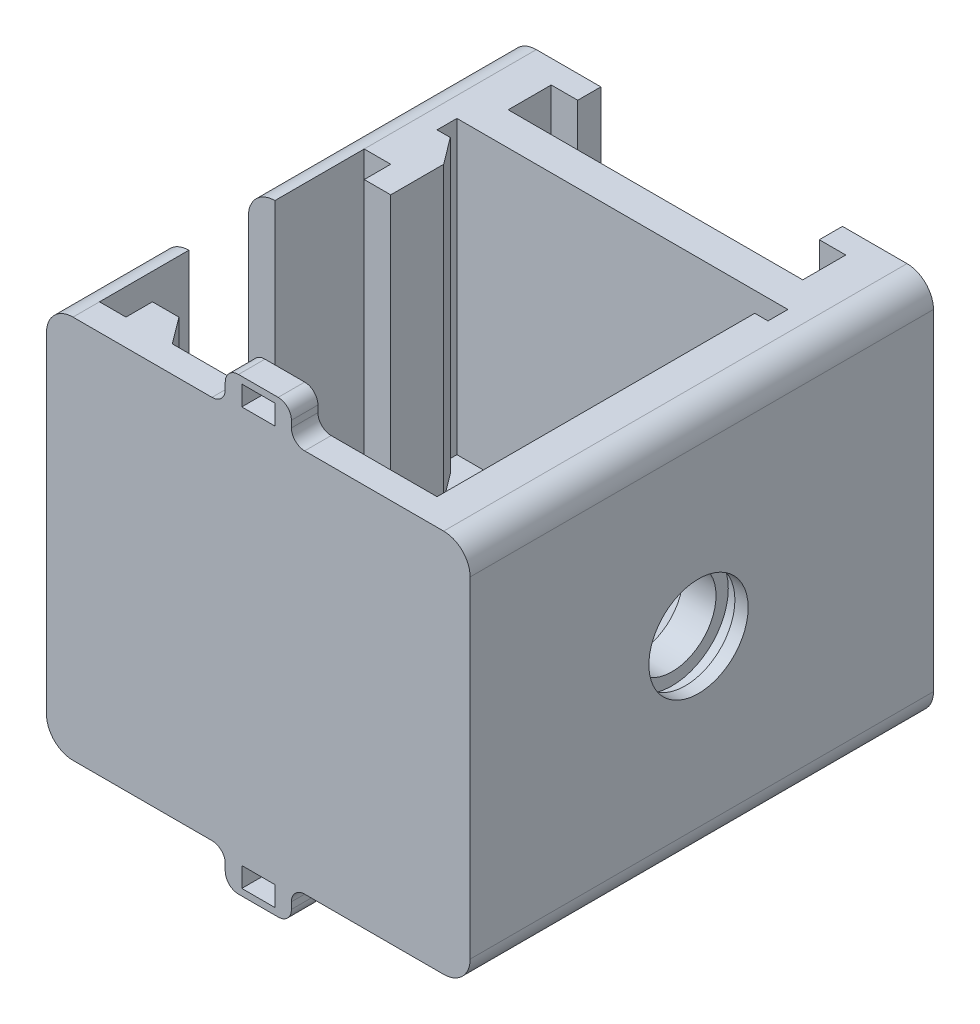
SolidWorks part; units mm, degrees
material "UNOBTANIUM"
ref_plane "Top Plane" through (0, 0, 0) normal (0, 0, 1) x (1, 0, 0)
ref_plane "Right Plane" through (0, 0, 0) normal (0, 1, 0) x (1, 0, 0)
ref_plane "Front Plane" through (0, 0, 0) normal (1, 0, 0) x (0, 0, -1)
ref_axis "x-axis" through (-17.6, 0, 0) along (1, 0, 0)
ref_axis "y-axis" through (0, -14.85, 0) along (0, 1, 0)
ref_axis "z-axis" through (0, 0, 36.75) along (0, 0, -1)
sketch "Sketch1" plane through (0, 0, 0) normal (0, 0, 1) x (1, 0, 0)
  line L1 (-16, 14.5) -> (16, 14.5)
  line L2 (-16, 14.5) -> (-16, -14.5)
  line L3 (-16, -14.5) -> (16, -14.5)
  line L4 (16, 14.5) -> (16, -14.5)
  line L5 (-16, 14.5) -> (16, -14.5) construction
  line L6 (-16, -14.5) -> (16, 14.5) construction
  point P0 (0, 0)
  dimension "D1" = 32
  dimension "D2" = 29
extrude "Boss-Extrude1" add sketch "Sketch1" along normal blind 35
fillet "Fillet1" radius 2 4 edges at (16, -14.5, 17.5) (16, 14.5, 17.5) (-16, -14.5, 17.5) (-16, 14.5, 17.5)
sketch "Sketch2" plane through (0, -14.5, 0) normal (0, -1, 0) x (1, 0, 0)
  line L0 (-9.125, 0) -> (-9.125, 1.75)
  line L1 (-14, 0) -> (14, 0) construction
  line L2 (-9.125, 1.75) -> (-11.125, 1.75)
  line L3 (-11.125, 1.75) -> (-11.125, 5)
  line L4 (-11.125, 5) -> (11.125, 5)
  line L5 (11.125, 5) -> (11.125, 1.75)
  line L6 (11.125, 1.75) -> (9.125, 1.75)
  line L7 (9.125, 1.75) -> (9.125, 0)
  line L9 (-9.125, 0) -> (9.125, 0)
  point P4 (0, 0)
  dimension "D1" = 18.25
  dimension "D2" = 1.75
  dimension "D3" = 3.25
  dimension "D4" = 22.25
extrude "Slot for Coil" cut sketch "Sketch2" against normal through all both and the other way through all
sketch "Sketch3" plane through (0, -14.5, 0) normal (0, -1, 0) x (1, 0, 0)
  line L0 (-9.125, 0) -> (-9.125, 1.75)
  line L1 (-9.125, 1.75) -> (-11.125, 1.75)
  line L2 (-11.125, 1.75) -> (-11.125, 5)
  line L3 (-11.125, 5) -> (11.125, 5)
  line L4 (11.125, 5) -> (11.125, 1.75)
  line L5 (11.125, 1.75) -> (9.125, 1.75)
  line L6 (9.125, 1.75) -> (9.125, 0)
  line L7 (9.125, 0) -> (-9.125, 0)
extrude "Boss-Extrude2" add sketch "Sketch3" against normal blind 7
sketch "Sketch4" plane through (0, 0, 1.75) normal (0, 0, -1) x (-1, 0, 0)
  line L1 (-9.125, 7.5) -> (-9.125, 6.5)
  line L2 (-9.125, 14.5) -> (-9.125, -7.5) construction
  arc A0 (-9.125, 7.5) -> (-9.125, 6.5) centre (-9.5, 7) cw
  dimension "D1" = 0.625
  dimension "D2" = 0.25
  dimension "D3" = 7
extrude "Boss-Extrude3" add sketch "Sketch4" along normal up to surface (1.75 mm away) up to face at (0, 1.1667, 0)
mirror "Mirror1" about plane through (0, 0, 0) normal (1, 0, 0) of "Boss-Extrude3"
sketch "Sketch5" plane through (0, 0, 0) normal (0, 0, -1) x (-1, 0, 0)
  line L0 (9.125, -7.5) -> (-9.125, -7.5) construction
  line L1 (-1, -7.5) -> (1, -7.5)
  line L2 (-1, -7.5) -> (-1, -14.5)
  line L3 (-1, -14.5) -> (1, -14.5)
  line L4 (1, -7.5) -> (1, -14.5)
  line L5 (14, -14.5) -> (-14, -14.5) construction
  point P8 (0, -7.5)
  dimension "D1" = 2
extrude "Cut-Extrude2" cut sketch "Sketch5" against normal offset from surface (33 mm away) 2 up to face at (0, 0, 35)
sketch "Sketch6" plane through (0, 14.5, 0) normal (0, 1, 0) x (1, 0, 0)
  line L0 (-12.5, -7.5) -> (-12.5, -9)
  line L1 (-12.5, -9) -> (-11.5, -9)
  line L2 (-11.5, -9) -> (-11.5, -33)
  line L3 (-11.5, -33) -> (11.5, -33)
  line L4 (11.5, -33) -> (11.5, -9)
  line L5 (11.5, -9) -> (12.5, -9)
  line L6 (12.5, -9) -> (12.5, -7.5)
  line L7 (12.5, -7.5) -> (-12.5, -7.5)
  line L8 (11.125, -5) -> (-11.125, -5) construction
  line L9 (0, -7.5) -> (0, -5) construction
  line L10 (14, -35) -> (-14, -35) construction
  dimension "D1" = 2.5
  dimension "D2" = 1.5
  dimension "D3" = 1
  dimension "D4" = 25
  dimension "D5" = 2
extrude "Cut-Extrude3" cut sketch "Sketch6" against normal up to surface (22 mm away) up to face at (7.0833, -7.5, 2.25)
sketch "Sketch7" plane through (0, -14.5, 0) normal (0, -1, 0) x (1, 0, 0)
  line L0 (1, 0) -> (14, 0) construction
  line L1 (1, 0) -> (-1, 0)
  line L2 (1, 0) -> (1, 33)
  line L3 (1, 33) -> (-1, 33)
  line L4 (-1, 0) -> (-1, 33)
  line L5 (1, 33) -> (1, 0) construction
extrude "Boss-Extrude4" add sketch "Sketch7" against normal blind 0.25
fillet "Fillet2" radius 6 1 edges at (0, -14.25, 33)
ref_axis "Axis1" through (63.07, 0, 17.75) along (-1, 0, 0)
ref_plane "Plane1" through (0, 0, 17.75) normal (0, 0, -1) x (-1, 0, 0)
sketch "Sketch9" plane through (0, 0, 17.75) normal (0, 0, -1) x (-1, 0, 0)
  line L0 (-15, 4.25) -> (-14, 4.25)
  line L1 (-16, -12.5) -> (-16, 12.5) construction
  line L2 (-14, 4.25) -> (-14, 3.325)
  line L3 (-14, 3.325) -> (-11.5, 3.325)
  line L4 (-11.5, 3.325) -> (-11.5, 0)
  line L5 (-63.07, 0) -> (46.93, 0) construction
  line L6 (-11.5, 0) -> (-16, 0)
  line L8 (-16, 0) -> (-0.664, 0) construction
  line L9 (-11.5, -7.5) -> (-11.5, 14.5) construction
  line L10 (-15, 4.25) -> (-15, 3.75)
  line L11 (-15, 3.75) -> (-16, 3.75)
  line L12 (-16, 3.75) -> (-16, 0)
  dimension "D1" = 6.65
  dimension "D2" = 8.5
  dimension "D3" = 1
  dimension "D4" = 1
  dimension "D5" = 7.5
revolve "Cut-Revolve1" cut sketch "Sketch9" angle 360 about L8
sketch "Sketch10" plane through (0, 14.5, 0) normal (0, 1, 0) x (1, 0, 0)
  line L0 (11.5, -31) -> (13.5, -31)
  line L1 (11.5, -9) -> (11.5, -33) construction
  line L2 (13.5, -31) -> (13.5, -33)
  line L3 (13.5, -33) -> (11.5, -33)
  line L4 (11.5, -33) -> (11.5, -31)
  dimension "D1" = 2
  dimension "D2" = 2
extrude "Cut-Extrude4" [suppressed] cut sketch "Sketch10" against normal up to surface (20 mm away)
mirror "Mirror2" [suppressed] about plane through (0, 0, 0) normal (1, 0, 0)
sketch "Sketch11" plane through (-16, 0, 44) normal (1, 0, 0) x (0, 0, -1)
  line L0 (21, 25) -> (21, 0) construction
  line L4 (24.25, 25) -> (24.25, 0)
  line L5 (17.75, 25) -> (17.75, 0)
  line L6 (9, 12.5) -> (44, 12.5) construction
  line L7 (21, 0) -> (44, 0) construction
  line L8 (9, 12.5) -> (9, -12.5) construction
  arc A2 (24.25, 25) -> (17.75, 25) centre (21, 25) ccw
  arc A3 (17.75, 0) -> (24.25, 0) centre (21, 0) ccw
  point P2 (21, 12.5)
  dimension "D1" = 6.5
  dimension "D2" = 12
extrude "Cut-Extrude5" cut sketch "Sketch11" along normal up to surface (4.5 mm away) up to face at (-11.5, 3.5, 21)
sketch "Sketch14" plane through (0, 14.5, 0) normal (0, 1, 0) x (1, 0, 0)
  line L0 (-11.5, -9) -> (-11.5, -19.75) construction
  line L1 (-11.5, -13) -> (-14, -13)
  line L2 (-11.5, -13) -> (-11.5, -33)
  line L3 (-11.5, -33) -> (-14, -33)
  line L4 (-14, -13) -> (-14, -33)
  line L5 (-16, -35) -> (-16, -26.25) construction
  line L6 (-11.5, -26.25) -> (-11.5, -19.75) construction
  point P12 (-11.5, -23)
  dimension "D1" = 2
extrude "Cut-Extrude6" cut sketch "Sketch14" against normal up to surface (22 mm away) up to face at (-8.3333, -7.5, 16.5)
sketch "Sketch16" plane through (0, 14.5, 0) normal (0, 1, 0) x (1, 0, 0)
  line L1 (-12, -11) -> (-10, -11)
  line L2 (-12, -11) -> (-12, -15)
  line L3 (-12, -15) -> (-10, -15)
  line L4 (-10, -11) -> (-10, -15)
  line L5 (-14, -33) -> (-14, -13) construction
  line L6 (-12, -33) -> (-12, -31)
  line L7 (-14, -33) -> (11.5, -33) construction
  line L8 (-12, -31) -> (-10, -31)
  line L9 (-10, -31) -> (-10, -33)
  line L10 (-10, -33) -> (-12, -33)
  line L11 (-12.5, -9) -> (-11.5, -9) construction
  line L13 (-11.5, -13) -> (-14, -13) construction
  line L14 (-14, -13) -> (-14, -19.75) construction
  dimension "D1" = 4
  dimension "D2" = 2
  dimension "D3" = 2
  dimension "D4" = 2
  dimension "D5" = 2
extrude "Boss-Extrude5" add sketch "Sketch16" against normal up to surface (22 mm away) up to face at (8.3333, -7.5, 16.5)
sketch "Sketch20" plane through (0, 14.5, 0) normal (0, 1, 0) x (1, 0, 0)
  line L0 (-11.5, -9) -> (-10, -11)
  line L1 (-10, -11) -> (-11.5, -11)
  line L2 (-11.5, -11) -> (-11.5, -9)
  line L3 (-10, -31) -> (-8.5, -33)
  line L4 (-1, -33) -> (-10, -33) construction
  line L5 (-8.5, -33) -> (-10, -33)
  line L6 (-10, -33) -> (-10, -31)
extrude "Boss-Extrude6" add sketch "Sketch20" against normal up to surface (22 mm away) up to face at (8.3333, -7.5, 16.5)
sketch "Sketch21" plane through (0, 14.5, 0) normal (0, 1, 0) x (-1, 0, 0)
  line L0 (0, 0) -> (0, 35) construction
  line L1 (-14, 35) -> (14, 35) construction
  line L2 (8.5, 33) -> (-11.5, 33) construction
  line L3 (-2.5, 35) -> (2.5, 35)
  line L4 (-2.5, 35) -> (-2.5, 33)
  line L5 (-2.5, 33) -> (2.5, 33)
  line L6 (2.5, 35) -> (2.5, 33)
  point P12 (0, 35)
  dimension "D1" = 5
extrude "Boss-Extrude7" add sketch "Sketch21" along normal blind 2.5
sketch "Sketch23" plane through (0, 0, 35) normal (0, 0, 1) x (1, 0, 0)
  line L0 (0, 0) -> (0, 17) construction
  line L3 (-1.25, 16.5) -> (1.25, 16.5)
  line L4 (-1.25, 16.5) -> (-1.25, 15)
  line L5 (-1.25, 15) -> (1.25, 15)
  line L6 (1.25, 16.5) -> (1.25, 15)
  line L7 (-2.5, 17) -> (2.5, 17) construction
  point P3 (0, 16.5)
  dimension "D1" = 1.5
  dimension "D2" = 2.5
  dimension "D3" = 0.5
extrude "Cut-Extrude7" cut sketch "Sketch23" against normal up to next
mirror "Mirror3" about plane through (0, 0, 0) normal (0, 1, 0) of "Boss-Extrude7", "Cut-Extrude7"
fillet "Fillet3" radius 1 8 edges at (-2.5, 14.5, 34) (2.5, 14.5, 34) (2.5, 17, 34) (-2.5, 17, 34) (2.5, -14.5, 34) (-2.5, -14.5, 34) (2.5, -17, 34) (-2.5, -17, 34)
